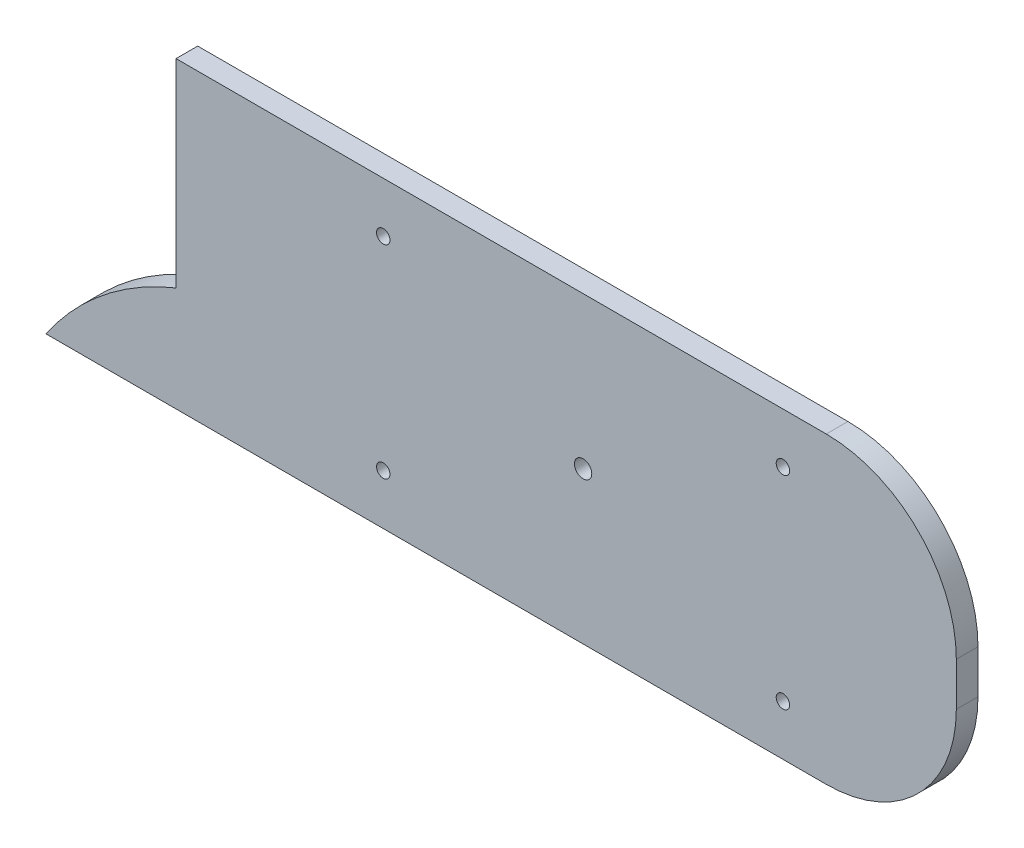
SolidWorks part; units mm, degrees
material "1060 Alloy"
ref_plane "Front Plane" through (0, 0, 0) normal (0, 0, 1) x (1, 0, 0)
ref_plane "Top Plane" through (0, 0, 0) normal (0, 1, 0) x (1, 0, 0)
ref_plane "Right Plane" through (0, 0, 0) normal (1, 0, 0) x (0, 0, -1)
sketch "Sketch2" plane through (0, 0, 0) normal (0, 0, 1) x (1, 0, 0)
  line L0 (0, 0) -> (457.2, 0)
  line L1 (76.2, 0) -> (76.2, 142.4009) construction
  line L2 (152.4, 0) -> (152.4, 186.487) construction
  line L9 (457.2, 177.8) -> (152.4, 177.8)
  line L14 (533.4, 76.2) -> (533.4, 101.6)
  line L15 (152.4, 177.8) -> (76.2, 177.8)
  line L16 (76.2, 177.8) -> (76.2, 61.4013)
  arc A5 (0, 0) -> (76.2, 61.4013) centre (138.3869, -93.7571) cw
  arc A6 (457.2, 0) -> (533.4, 76.2) centre (457.2, 76.2) ccw
  arc A7 (533.4, 101.6) -> (457.2, 177.8) centre (457.2, 101.6) ccw
  dimension "D6" = 167.1566
  dimension "D7" = 142.4009
  dimension "D5" = 177.8
  dimension "D1" = 76.2
  dimension "D4" = 457.2
  dimension "D9" = 138.3869
  dimension "D2" = 76.2
  dimension "D3" = 152.4
  dimension "D8" = 186.487
extrude "Boss-Extrude1" add sketch "Sketch2" along normal blind 12.7
sketch "Sketch4" plane through (0, 0, 12.7) normal (0, 0, 1) x (1, 0, 0)
  line L0 (314.706, 0) -> (314.706, 177.8) construction
  line L1 (0, 0) -> (457.2, 0) construction
  line L2 (457.2, 177.8) -> (76.2, 177.8) construction
  line L3 (76.2, 88.9) -> (533.4, 88.9) construction
  line L4 (76.2, 177.8) -> (76.2, 61.4013) construction
  line L6 (533.4, 76.2) -> (533.4, 101.6) construction
  circle A0 centre (314.706, 88.9) radius 5.08
  circle A3 centre (431.8, 148.336) radius 3.937
  circle A5 centre (197.612, 148.336) radius 3.937
  circle A6 centre (197.612, 29.464) radius 3.937
  circle A7 centre (431.8, 29.464) radius 3.937
  dimension "D1" = 10.16
  dimension "D4" = 7.874
  dimension "D5" = 29.464
  dimension "D6" = 117.094
  dimension "D2" = 314.706
  dimension "D3" = 88.9
extrude "Cut-Extrude2" cut sketch "Sketch4" against normal through all
equation "\"0.5n\"=0.25"
equation "\".5n\"=0.25"
